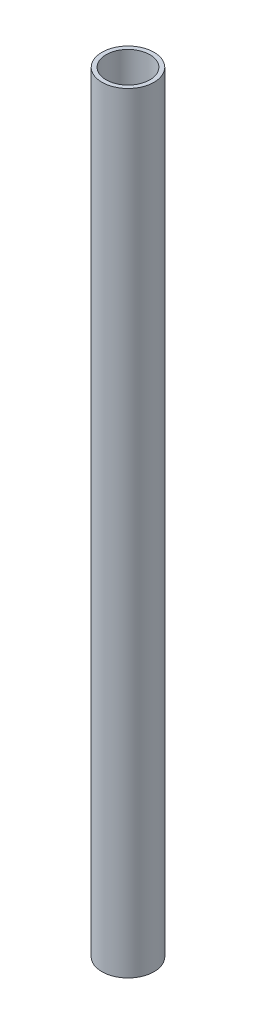
SolidWorks part; units mm, degrees
material "Thornel VCB-20 Carbon Cloth"
ref_plane "Front Plane" through (0, 0, 0) normal (0, 0, 1) x (1, 0, 0)
ref_plane "Top Plane" through (0, 0, 0) normal (0, 1, 0) x (1, 0, 0)
ref_plane "Right Plane" through (0, 0, 0) normal (1, 0, 0) x (0, 0, -1)
sketch "Sketch1" plane through (0, 0, 0) normal (0, 1, 0) x (1, 0, 0)
  circle A0 centre (0, 0) radius 12.5
  circle A1 centre (0, 0) radius 10.5
  dimension "D1" = 25
  dimension "D2" = 21
extrude "Boss-Extrude1" add sketch "Sketch1" along normal blind 370
sketch "Sketch2" [suppressed] plane through (0, 0, 0) normal (0, 0, 1) x (1, 0, 0)
  line L0 (0, 0) -> (106.9072, 0) construction
sketch "Sketch3" plane through (0, 0, 0) normal (1, 0, 0) x (0, 0, -1)
  line L0 (12.5, 370) -> (-12.5, 370) construction
  line L1 (12.5, 370) -> (-12.5, 370)
  circle A0 centre (0, 370) radius 3.3557
extrude "Boss-Extrude2" [suppressed] add sketch "Sketch3" along normal blind 18 contours A0
